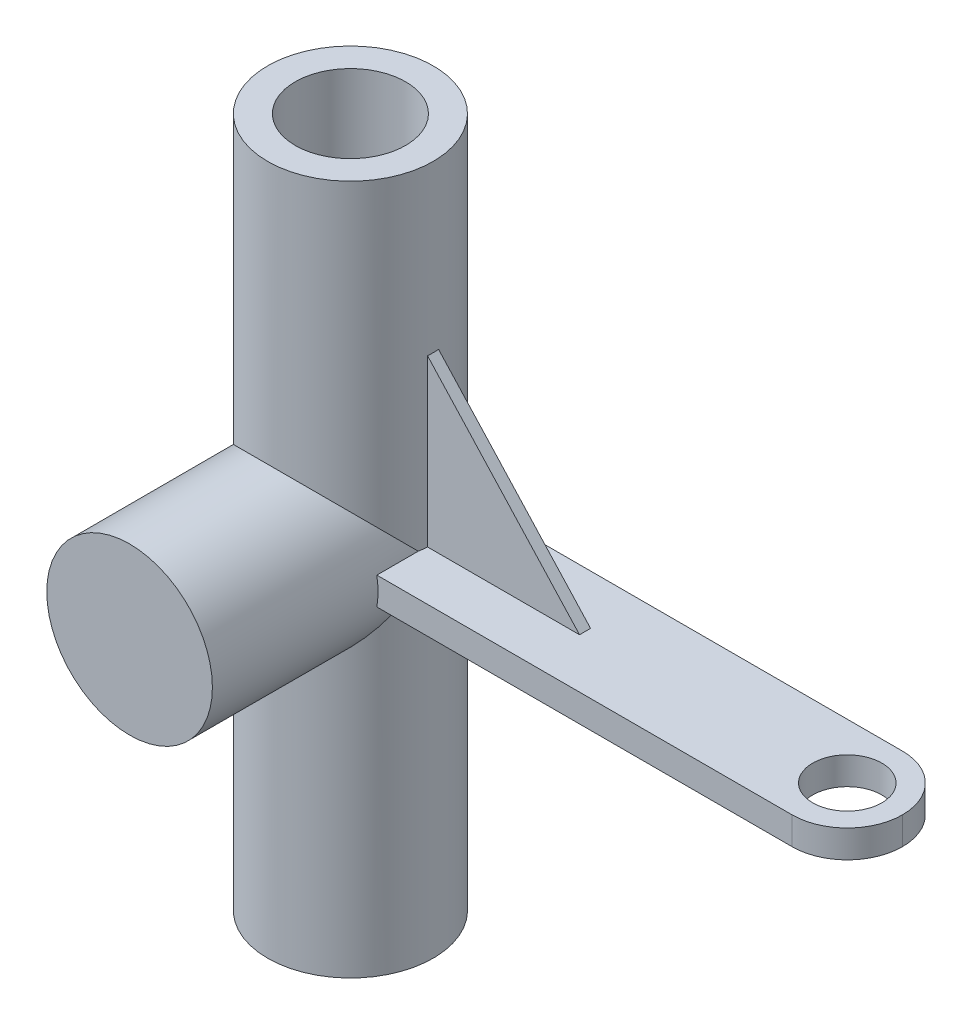
SolidWorks part; units mm, degrees
ref_plane "Front Plane" through (0, 0, 0) normal (0, 0, 1) x (1, 0, 0)
ref_plane "Top Plane" through (0, 0, 0) normal (0, 1, 0) x (1, 0, 0)
ref_plane "Right Plane" through (0, 0, 0) normal (1, 0, 0) x (0, 0, -1)
sketch "Sketch1" plane through (0, 0, 0) normal (0, 1, 0) x (1, 0, 0)
  circle A0 centre (0, 0) radius 10
  circle A1 centre (0, 0) radius 15
  dimension "D1" = 20
  dimension "D2" = 5
extrude "Boss-Extrude1" add sketch "Sketch1" along normal blind 125
sketch "Sketch2" plane through (0, 0, 0) normal (0, 0, 1) x (1, 0, 0)
  line L0 (0, 125) -> (0, 0) construction
  line L1 (10, 125) -> (-10, 125) construction
  circle A0 centre (0, 62.5) radius 15
  dimension "D1" = 30
extrude "Boss-Extrude2" add sketch "Sketch2" along normal blind 40
sketch "Sketch6" plane through (0, 0, 0) normal (1, 0, 0) x (0, 0, -1)
  line L0 (15, 0) -> (15, 125) construction
  line L5 (-10, 65) -> (10, 65)
  line L6 (10, 65) -> (10, 60)
  line L7 (10, 60) -> (-10, 60)
  line L8 (-10, 60) -> (-10, 65)
  line L9 (-15, 77.5) -> (-40, 77.5) construction
  dimension "D1" = 12.5
  dimension "D2" = 20
  dimension "D3" = 5
  dimension "D4" = 5
extrude "Boss-Extrude6" add sketch "Sketch6" along normal blind 100
fillet "Fillet1" radius 10 2 edges at (100, 62.5, -10) (100, 62.5, 10)
sketch "Sketch8" plane through (0, 65, 0) normal (0, 1, 0) x (1, 0, 0)
  line L0 (14.5, 1) -> (14.5, -1)
  line L1 (14.5, 1) -> (42.5, 1)
  line L2 (42.5, 1) -> (42.5, -1)
  line L3 (14.5, -1) -> (42.5, -1)
  line L6 (90, -10) -> (14.7902, -10) construction
  dimension "D1" = 14.5
  dimension "D2" = 2
  dimension "D3" = 9
  dimension "D4" = 28
extrude "Boss-Extrude7" add sketch "Sketch8" along normal blind 30
sketch "Sketch9" plane through (0, 0, -1) normal (0, 0, -1) x (-1, 0, 0)
  line L0 (-14.9666, 95) -> (-42.5, 65)
  line L1 (-42.5, 65) -> (-42.5, 95)
  line L2 (-42.5, 95) -> (-14.9666, 95)
extrude "Cut-Extrude1" cut sketch "Sketch9" against normal blind 30
sketch "Sketch10" plane through (0, 65, 0) normal (0, 1, 0) x (1, 0, 0)
  circle A0 centre (90, 0) radius 6.25
  dimension "D2" = 12.5
extrude "Cut-Extrude2" cut sketch "Sketch10" against normal blind 30
